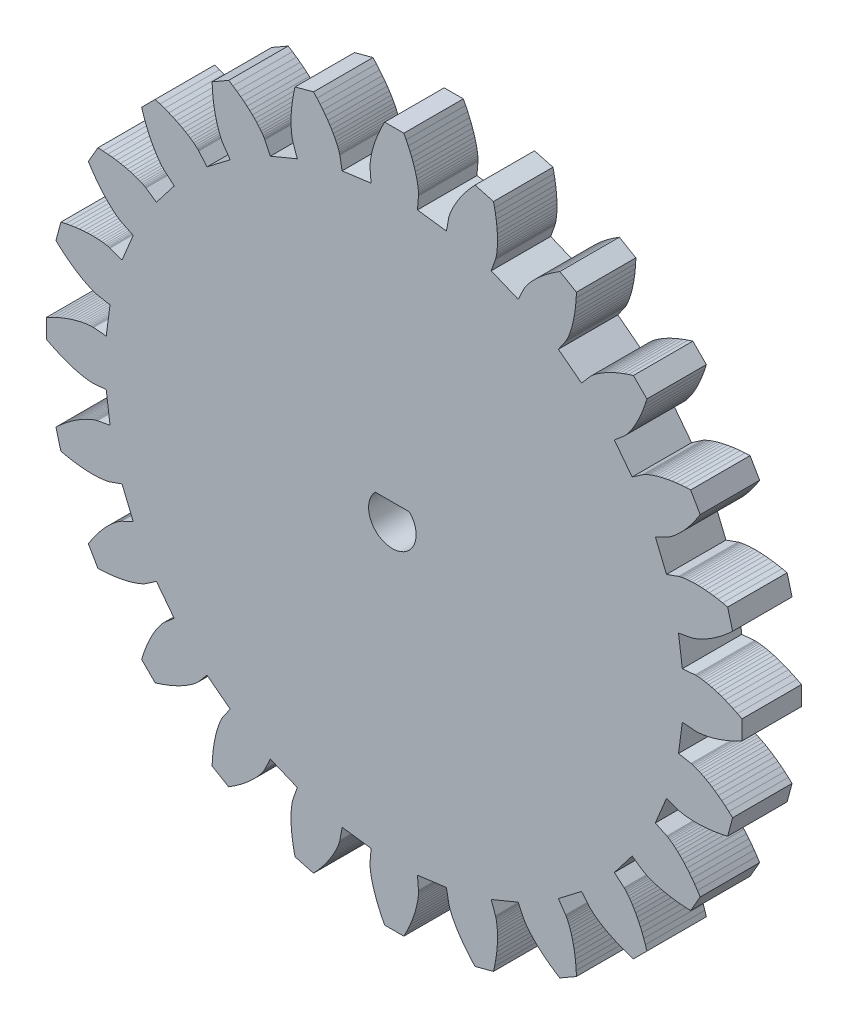
SolidWorks part; units mm, degrees
ref_plane "Front Plane" through (0, 0, 0) normal (0, 0, 1) x (1, 0, 0)
ref_plane "Top Plane" through (0, 0, 0) normal (0, 1, 0) x (1, 0, 0)
ref_plane "Right Plane" through (0, 0, 0) normal (1, 0, 0) x (0, 0, -1)
sketch "Model" plane through (0, 0, 0) normal (0, 0, 1) x (1, 0, 0)
  line L0 (24.2216, 1.9505) -> (25.2898, 2.0365)
  line L1 (25.2898, 2.0365) -> (25.3014, 2.0372)
  line L2 (25.3014, 2.0372) -> (25.3361, 2.0384)
  line L3 (25.3361, 2.0384) -> (25.3939, 2.0386)
  line L4 (25.3939, 2.0386) -> (25.4748, 2.0365)
  line L5 (25.4748, 2.0365) -> (25.5787, 2.0307)
  line L6 (25.5787, 2.0307) -> (25.7054, 2.0197)
  line L7 (25.7054, 2.0197) -> (25.8547, 2.0023)
  line L8 (25.8547, 2.0023) -> (26.0263, 1.977)
  line L9 (26.0263, 1.977) -> (26.2199, 1.9424)
  line L10 (26.2199, 1.9424) -> (26.4349, 1.8973)
  line L11 (26.4349, 1.8973) -> (26.671, 1.8403)
  line L12 (26.671, 1.8403) -> (26.9275, 1.7702)
  line L13 (26.9275, 1.7702) -> (27.2039, 1.6855)
  line L14 (27.2039, 1.6855) -> (27.4996, 1.5851)
  line L15 (27.4996, 1.5851) -> (27.8137, 1.4677)
  line L16 (27.8137, 1.4677) -> (28.1456, 1.3321)
  line L17 (28.1456, 1.3321) -> (28.4943, 1.1772)
  line L18 (28.4943, 1.1772) -> (28.8591, 1.0018)
  line L19 (28.8591, 1.0018) -> (29.2389, 0.8049)
  line L20 (29.2389, 0.8049) -> (29.2389, -0.8049)
  line L21 (29.2389, -0.8049) -> (28.8591, -1.0018)
  line L22 (28.8591, -1.0018) -> (28.4943, -1.1772)
  line L23 (28.4943, -1.1772) -> (28.1456, -1.3321)
  line L24 (28.1456, -1.3321) -> (27.8137, -1.4677)
  line L25 (27.8137, -1.4677) -> (27.4996, -1.5851)
  line L26 (27.4996, -1.5851) -> (27.2039, -1.6855)
  line L27 (27.2039, -1.6855) -> (26.9275, -1.7702)
  line L28 (26.9275, -1.7702) -> (26.671, -1.8403)
  line L29 (26.671, -1.8403) -> (26.4349, -1.8973)
  line L30 (26.4349, -1.8973) -> (26.2199, -1.9424)
  line L31 (26.2199, -1.9424) -> (26.0263, -1.977)
  line L32 (26.0263, -1.977) -> (25.8547, -2.0023)
  line L33 (25.8547, -2.0023) -> (25.7054, -2.0197)
  line L34 (25.7054, -2.0197) -> (25.5787, -2.0307)
  line L35 (25.5787, -2.0307) -> (25.4748, -2.0365)
  line L36 (25.4748, -2.0365) -> (25.3939, -2.0386)
  line L37 (25.3939, -2.0386) -> (25.3361, -2.0384)
  line L38 (25.3361, -2.0384) -> (25.3014, -2.0372)
  line L39 (25.3014, -2.0372) -> (25.2898, -2.0365)
  line L40 (25.2898, -2.0365) -> (24.2216, -1.9505)
  line L41 (24.2216, -1.9505) -> (23.9011, -4.385)
  line L42 (23.9011, -4.385) -> (24.9552, -4.5784)
  line L43 (24.9552, -4.5784) -> (24.9665, -4.5807)
  line L44 (24.9665, -4.5807) -> (25.0003, -4.5885)
  line L45 (25.0003, -4.5885) -> (25.0562, -4.6033)
  line L46 (25.0562, -4.6033) -> (25.1338, -4.6263)
  line L47 (25.1338, -4.6263) -> (25.2327, -4.6588)
  line L48 (25.2327, -4.6588) -> (25.3523, -4.7022)
  line L49 (25.3523, -4.7022) -> (25.492, -4.7576)
  line L50 (25.492, -4.7576) -> (25.6512, -4.8265)
  line L51 (25.6512, -4.8265) -> (25.8292, -4.91)
  line L52 (25.8292, -4.91) -> (26.0252, -5.0092)
  line L53 (26.0252, -5.0092) -> (26.2385, -5.1253)
  line L54 (26.2385, -5.1253) -> (26.4681, -5.2595)
  line L55 (26.4681, -5.2595) -> (26.7132, -5.4128)
  line L56 (26.7132, -5.4128) -> (26.9728, -5.5864)
  line L57 (26.9728, -5.5864) -> (27.2458, -5.781)
  line L58 (27.2458, -5.781) -> (27.5313, -5.9979)
  line L59 (27.5313, -5.9979) -> (27.8281, -6.2378)
  line L60 (27.8281, -6.2378) -> (28.135, -6.5016)
  line L61 (28.135, -6.5016) -> (28.4509, -6.7901)
  line L62 (28.4509, -6.7901) -> (28.0343, -8.3451)
  line L63 (28.0343, -8.3451) -> (27.6164, -8.437)
  line L64 (27.6164, -8.437) -> (27.2187, -8.512)
  line L65 (27.2187, -8.512) -> (26.8417, -8.5713)
  line L66 (26.8417, -8.5713) -> (26.4861, -8.6164)
  line L67 (26.4861, -8.6164) -> (26.1523, -8.6485)
  line L68 (26.1523, -8.6485) -> (25.8407, -8.6689)
  line L69 (25.8407, -8.6689) -> (25.5518, -8.6792)
  line L70 (25.5518, -8.6792) -> (25.2859, -8.6806)
  line L71 (25.2859, -8.6806) -> (25.0431, -8.6745)
  line L72 (25.0431, -8.6745) -> (24.8237, -8.6625)
  line L73 (24.8237, -8.6625) -> (24.6278, -8.6457)
  line L74 (24.6278, -8.6457) -> (24.4555, -8.6258)
  line L75 (24.4555, -8.6258) -> (24.3068, -8.604)
  line L76 (24.3068, -8.604) -> (24.1816, -8.5817)
  line L77 (24.1816, -8.5817) -> (24.0797, -8.5605)
  line L78 (24.0797, -8.5605) -> (24.001, -8.5416)
  line L79 (24.001, -8.5416) -> (23.9452, -8.5264)
  line L80 (23.9452, -8.5264) -> (23.912, -8.5163)
  line L81 (23.912, -8.5163) -> (23.901, -8.5126)
  line L82 (23.901, -8.5126) -> (22.8914, -8.1531)
  line L83 (22.8914, -8.1531) -> (21.9518, -10.4216)
  line L84 (21.9518, -10.4216) -> (22.9199, -10.8812)
  line L85 (22.9199, -10.8812) -> (22.9302, -10.8864)
  line L86 (22.9302, -10.8864) -> (22.9609, -10.9027)
  line L87 (22.9609, -10.9027) -> (23.011, -10.9314)
  line L88 (23.011, -10.9314) -> (23.0801, -10.9737)
  line L89 (23.0801, -10.9737) -> (23.1671, -11.0307)
  line L90 (23.1671, -11.0307) -> (23.2714, -11.1036)
  line L91 (23.2714, -11.1036) -> (23.392, -11.1933)
  line L92 (23.392, -11.1933) -> (23.528, -11.3011)
  line L93 (23.528, -11.3011) -> (23.6783, -11.4277)
  line L94 (23.6783, -11.4277) -> (23.842, -11.5743)
  line L95 (23.842, -11.5743) -> (24.0179, -11.7417)
  line L96 (24.0179, -11.7417) -> (24.205, -11.9308)
  line L97 (24.205, -11.9308) -> (24.402, -12.1423)
  line L98 (24.402, -12.1423) -> (24.6078, -12.3771)
  line L99 (24.6078, -12.3771) -> (24.8212, -12.6358)
  line L100 (24.8212, -12.6358) -> (25.0408, -12.9191)
  line L101 (25.0408, -12.9191) -> (25.2654, -13.2277)
  line L102 (25.2654, -13.2277) -> (25.4936, -13.5619)
  line L103 (25.4936, -13.5619) -> (25.7241, -13.9224)
  line L104 (25.7241, -13.9224) -> (24.9192, -15.3165)
  line L105 (24.9192, -15.3165) -> (24.4918, -15.2972)
  line L106 (24.4918, -15.2972) -> (24.0882, -15.2667)
  line L107 (24.0882, -15.2667) -> (23.7087, -15.2264)
  line L108 (23.7087, -15.2264) -> (23.3535, -15.1779)
  line L109 (23.3535, -15.1779) -> (23.0228, -15.1225)
  line L110 (23.0228, -15.1225) -> (22.7165, -15.0616)
  line L111 (22.7165, -15.0616) -> (22.4348, -14.9967)
  line L112 (22.4348, -14.9967) -> (22.1776, -14.9293)
  line L113 (22.1776, -14.9293) -> (21.9446, -14.8606)
  line L114 (21.9446, -14.8606) -> (21.7359, -14.7921)
  line L115 (21.7359, -14.7921) -> (21.551, -14.7253)
  line L116 (21.551, -14.7253) -> (21.3897, -14.6614)
  line L117 (21.3897, -14.6614) -> (21.2517, -14.6018)
  line L118 (21.2517, -14.6018) -> (21.1365, -14.548)
  line L119 (21.1365, -14.548) -> (21.0436, -14.5011)
  line L120 (21.0436, -14.5011) -> (20.9724, -14.4624)
  line L121 (20.9724, -14.4624) -> (20.9225, -14.4333)
  line L122 (20.9225, -14.4333) -> (20.893, -14.415)
  line L123 (20.893, -14.415) -> (20.8834, -14.4086)
  line L124 (20.8834, -14.4086) -> (20.0013, -13.8)
  line L125 (20.0013, -13.8) -> (18.5065, -15.748)
  line L126 (18.5065, -15.748) -> (19.3227, -16.4426)
  line L127 (19.3227, -16.4426) -> (19.3313, -16.4502)
  line L128 (19.3313, -16.4502) -> (19.3566, -16.4739)
  line L129 (19.3566, -16.4739) -> (19.3977, -16.5147)
  line L130 (19.3977, -16.5147) -> (19.4534, -16.5734)
  line L131 (19.4534, -16.5734) -> (19.5228, -16.651)
  line L132 (19.5228, -16.651) -> (19.6046, -16.7483)
  line L133 (19.6046, -16.7483) -> (19.6979, -16.8662)
  line L134 (19.6979, -16.8662) -> (19.8013, -17.0055)
  line L135 (19.8013, -17.0055) -> (19.9138, -17.1667)
  line L136 (19.9138, -17.1667) -> (20.0339, -17.3507)
  line L137 (20.0339, -17.3507) -> (20.1605, -17.5579)
  line L138 (20.1605, -17.5579) -> (20.2923, -17.7889)
  line L139 (20.2923, -17.7889) -> (20.4279, -18.0443)
  line L140 (20.4279, -18.0443) -> (20.5659, -18.3243)
  line L141 (20.5659, -18.3243) -> (20.7051, -18.6294)
  line L142 (20.7051, -18.6294) -> (20.8439, -18.96)
  line L143 (20.8439, -18.96) -> (20.9809, -19.3161)
  line L144 (20.9809, -19.3161) -> (21.1149, -19.698)
  line L145 (21.1149, -19.698) -> (21.2442, -20.1059)
  line L146 (21.2442, -20.1059) -> (20.1059, -21.2442)
  line L147 (20.1059, -21.2442) -> (19.698, -21.1149)
  line L148 (19.698, -21.1149) -> (19.3161, -20.9809)
  line L149 (19.3161, -20.9809) -> (18.96, -20.8439)
  line L150 (18.96, -20.8439) -> (18.6294, -20.7051)
  line L151 (18.6294, -20.7051) -> (18.3243, -20.5659)
  line L152 (18.3243, -20.5659) -> (18.0443, -20.4279)
  line L153 (18.0443, -20.4279) -> (17.7889, -20.2923)
  line L154 (17.7889, -20.2923) -> (17.5579, -20.1605)
  line L155 (17.5579, -20.1605) -> (17.3507, -20.0339)
  line L156 (17.3507, -20.0339) -> (17.1667, -19.9138)
  line L157 (17.1667, -19.9138) -> (17.0055, -19.8013)
  line L158 (17.0055, -19.8013) -> (16.8662, -19.6979)
  line L159 (16.8662, -19.6979) -> (16.7483, -19.6046)
  line L160 (16.7483, -19.6046) -> (16.651, -19.5228)
  line L161 (16.651, -19.5228) -> (16.5734, -19.4534)
  line L162 (16.5734, -19.4534) -> (16.5147, -19.3977)
  line L163 (16.5147, -19.3977) -> (16.4739, -19.3566)
  line L164 (16.4739, -19.3566) -> (16.4502, -19.3313)
  line L165 (16.4502, -19.3313) -> (16.4426, -19.3227)
  line L166 (16.4426, -19.3227) -> (15.748, -18.5065)
  line L167 (15.748, -18.5065) -> (13.8, -20.0013)
  line L168 (13.8, -20.0013) -> (14.4086, -20.8834)
  line L169 (14.4086, -20.8834) -> (14.415, -20.893)
  line L170 (14.415, -20.893) -> (14.4333, -20.9225)
  line L171 (14.4333, -20.9225) -> (14.4624, -20.9724)
  line L172 (14.4624, -20.9724) -> (14.5011, -21.0436)
  line L173 (14.5011, -21.0436) -> (14.548, -21.1365)
  line L174 (14.548, -21.1365) -> (14.6018, -21.2517)
  line L175 (14.6018, -21.2517) -> (14.6614, -21.3897)
  line L176 (14.6614, -21.3897) -> (14.7253, -21.551)
  line L177 (14.7253, -21.551) -> (14.7921, -21.7359)
  line L178 (14.7921, -21.7359) -> (14.8606, -21.9446)
  line L179 (14.8606, -21.9446) -> (14.9293, -22.1776)
  line L180 (14.9293, -22.1776) -> (14.9967, -22.4348)
  line L181 (14.9967, -22.4348) -> (15.0616, -22.7165)
  line L182 (15.0616, -22.7165) -> (15.1225, -23.0228)
  line L183 (15.1225, -23.0228) -> (15.1779, -23.3535)
  line L184 (15.1779, -23.3535) -> (15.2264, -23.7087)
  line L185 (15.2264, -23.7087) -> (15.2667, -24.0882)
  line L186 (15.2667, -24.0882) -> (15.2972, -24.4918)
  line L187 (15.2972, -24.4918) -> (15.3165, -24.9192)
  line L188 (15.3165, -24.9192) -> (13.9224, -25.7241)
  line L189 (13.9224, -25.7241) -> (13.5619, -25.4936)
  line L190 (13.5619, -25.4936) -> (13.2277, -25.2654)
  line L191 (13.2277, -25.2654) -> (12.9191, -25.0408)
  line L192 (12.9191, -25.0408) -> (12.6358, -24.8212)
  line L193 (12.6358, -24.8212) -> (12.3771, -24.6078)
  line L194 (12.3771, -24.6078) -> (12.1423, -24.402)
  line L195 (12.1423, -24.402) -> (11.9308, -24.205)
  line L196 (11.9308, -24.205) -> (11.7417, -24.0179)
  line L197 (11.7417, -24.0179) -> (11.5743, -23.842)
  line L198 (11.5743, -23.842) -> (11.4277, -23.6783)
  line L199 (11.4277, -23.6783) -> (11.3011, -23.528)
  line L200 (11.3011, -23.528) -> (11.1933, -23.392)
  line L201 (11.1933, -23.392) -> (11.1036, -23.2714)
  line L202 (11.1036, -23.2714) -> (11.0307, -23.1671)
  line L203 (11.0307, -23.1671) -> (10.9737, -23.0801)
  line L204 (10.9737, -23.0801) -> (10.9314, -23.011)
  line L205 (10.9314, -23.011) -> (10.9027, -22.9609)
  line L206 (10.9027, -22.9609) -> (10.8864, -22.9302)
  line L207 (10.8864, -22.9302) -> (10.8812, -22.9199)
  line L208 (10.8812, -22.9199) -> (10.4216, -21.9518)
  line L209 (10.4216, -21.9518) -> (8.1531, -22.8914)
  line L210 (8.1531, -22.8914) -> (8.5126, -23.901)
  line L211 (8.5126, -23.901) -> (8.5163, -23.912)
  line L212 (8.5163, -23.912) -> (8.5264, -23.9452)
  line L213 (8.5264, -23.9452) -> (8.5416, -24.001)
  line L214 (8.5416, -24.001) -> (8.5605, -24.0797)
  line L215 (8.5605, -24.0797) -> (8.5817, -24.1816)
  line L216 (8.5817, -24.1816) -> (8.604, -24.3068)
  line L217 (8.604, -24.3068) -> (8.6258, -24.4555)
  line L218 (8.6258, -24.4555) -> (8.6457, -24.6278)
  line L219 (8.6457, -24.6278) -> (8.6625, -24.8237)
  line L220 (8.6625, -24.8237) -> (8.6745, -25.0431)
  line L221 (8.6745, -25.0431) -> (8.6806, -25.2859)
  line L222 (8.6806, -25.2859) -> (8.6792, -25.5518)
  line L223 (8.6792, -25.5518) -> (8.6689, -25.8407)
  line L224 (8.6689, -25.8407) -> (8.6485, -26.1523)
  line L225 (8.6485, -26.1523) -> (8.6164, -26.4861)
  line L226 (8.6164, -26.4861) -> (8.5713, -26.8417)
  line L227 (8.5713, -26.8417) -> (8.512, -27.2187)
  line L228 (8.512, -27.2187) -> (8.437, -27.6164)
  line L229 (8.437, -27.6164) -> (8.3451, -28.0343)
  line L230 (8.3451, -28.0343) -> (6.7901, -28.4509)
  line L231 (6.7901, -28.4509) -> (6.5016, -28.135)
  line L232 (6.5016, -28.135) -> (6.2378, -27.8281)
  line L233 (6.2378, -27.8281) -> (5.9979, -27.5313)
  line L234 (5.9979, -27.5313) -> (5.781, -27.2458)
  line L235 (5.781, -27.2458) -> (5.5864, -26.9728)
  line L236 (5.5864, -26.9728) -> (5.4128, -26.7132)
  line L237 (5.4128, -26.7132) -> (5.2595, -26.4681)
  line L238 (5.2595, -26.4681) -> (5.1253, -26.2385)
  line L239 (5.1253, -26.2385) -> (5.0092, -26.0252)
  line L240 (5.0092, -26.0252) -> (4.91, -25.8292)
  line L241 (4.91, -25.8292) -> (4.8265, -25.6512)
  line L242 (4.8265, -25.6512) -> (4.7576, -25.492)
  line L243 (4.7576, -25.492) -> (4.7022, -25.3523)
  line L244 (4.7022, -25.3523) -> (4.6588, -25.2327)
  line L245 (4.6588, -25.2327) -> (4.6263, -25.1338)
  line L246 (4.6263, -25.1338) -> (4.6033, -25.0562)
  line L247 (4.6033, -25.0562) -> (4.5885, -25.0003)
  line L248 (4.5885, -25.0003) -> (4.5807, -24.9665)
  line L249 (4.5807, -24.9665) -> (4.5784, -24.9552)
  line L250 (4.5784, -24.9552) -> (4.385, -23.9011)
  line L251 (4.385, -23.9011) -> (1.9505, -24.2216)
  line L252 (1.9505, -24.2216) -> (2.0365, -25.2898)
  line L253 (2.0365, -25.2898) -> (2.0372, -25.3014)
  line L254 (2.0372, -25.3014) -> (2.0384, -25.3361)
  line L255 (2.0384, -25.3361) -> (2.0386, -25.3939)
  line L256 (2.0386, -25.3939) -> (2.0365, -25.4748)
  line L257 (2.0365, -25.4748) -> (2.0307, -25.5787)
  line L258 (2.0307, -25.5787) -> (2.0197, -25.7054)
  line L259 (2.0197, -25.7054) -> (2.0023, -25.8547)
  line L260 (2.0023, -25.8547) -> (1.977, -26.0263)
  line L261 (1.977, -26.0263) -> (1.9424, -26.2199)
  line L262 (1.9424, -26.2199) -> (1.8973, -26.4349)
  line L263 (1.8973, -26.4349) -> (1.8403, -26.671)
  line L264 (1.8403, -26.671) -> (1.7702, -26.9275)
  line L265 (1.7702, -26.9275) -> (1.6855, -27.2039)
  line L266 (1.6855, -27.2039) -> (1.5851, -27.4996)
  line L267 (1.5851, -27.4996) -> (1.4677, -27.8137)
  line L268 (1.4677, -27.8137) -> (1.3321, -28.1456)
  line L269 (1.3321, -28.1456) -> (1.1772, -28.4943)
  line L270 (1.1772, -28.4943) -> (1.0018, -28.8591)
  line L271 (1.0018, -28.8591) -> (0.8049, -29.2389)
  line L272 (0.8049, -29.2389) -> (-0.8049, -29.2389)
  line L273 (-0.8049, -29.2389) -> (-1.0018, -28.8591)
  line L274 (-1.0018, -28.8591) -> (-1.1772, -28.4943)
  line L275 (-1.1772, -28.4943) -> (-1.3321, -28.1456)
  line L276 (-1.3321, -28.1456) -> (-1.4677, -27.8137)
  line L277 (-1.4677, -27.8137) -> (-1.5851, -27.4996)
  line L278 (-1.5851, -27.4996) -> (-1.6855, -27.2039)
  line L279 (-1.6855, -27.2039) -> (-1.7702, -26.9275)
  line L280 (-1.7702, -26.9275) -> (-1.8403, -26.671)
  line L281 (-1.8403, -26.671) -> (-1.8973, -26.4349)
  line L282 (-1.8973, -26.4349) -> (-1.9424, -26.2199)
  line L283 (-1.9424, -26.2199) -> (-1.977, -26.0263)
  line L284 (-1.977, -26.0263) -> (-2.0023, -25.8547)
  line L285 (-2.0023, -25.8547) -> (-2.0197, -25.7054)
  line L286 (-2.0197, -25.7054) -> (-2.0307, -25.5787)
  line L287 (-2.0307, -25.5787) -> (-2.0365, -25.4748)
  line L288 (-2.0365, -25.4748) -> (-2.0386, -25.3939)
  line L289 (-2.0386, -25.3939) -> (-2.0384, -25.3361)
  line L290 (-2.0384, -25.3361) -> (-2.0372, -25.3014)
  line L291 (-2.0372, -25.3014) -> (-2.0365, -25.2898)
  line L292 (-2.0365, -25.2898) -> (-1.9505, -24.2216)
  line L293 (-1.9505, -24.2216) -> (-4.385, -23.9011)
  line L294 (-4.385, -23.9011) -> (-4.5784, -24.9552)
  line L295 (-4.5784, -24.9552) -> (-4.5807, -24.9665)
  line L296 (-4.5807, -24.9665) -> (-4.5885, -25.0003)
  line L297 (-4.5885, -25.0003) -> (-4.6033, -25.0562)
  line L298 (-4.6033, -25.0562) -> (-4.6263, -25.1338)
  line L299 (-4.6263, -25.1338) -> (-4.6588, -25.2327)
  line L300 (-4.6588, -25.2327) -> (-4.7022, -25.3523)
  line L301 (-4.7022, -25.3523) -> (-4.7576, -25.492)
  line L302 (-4.7576, -25.492) -> (-4.8265, -25.6512)
  line L303 (-4.8265, -25.6512) -> (-4.91, -25.8292)
  line L304 (-4.91, -25.8292) -> (-5.0092, -26.0252)
  line L305 (-5.0092, -26.0252) -> (-5.1253, -26.2385)
  line L306 (-5.1253, -26.2385) -> (-5.2595, -26.4681)
  line L307 (-5.2595, -26.4681) -> (-5.4128, -26.7132)
  line L308 (-5.4128, -26.7132) -> (-5.5864, -26.9728)
  line L309 (-5.5864, -26.9728) -> (-5.781, -27.2458)
  line L310 (-5.781, -27.2458) -> (-5.9979, -27.5313)
  line L311 (-5.9979, -27.5313) -> (-6.2378, -27.8281)
  line L312 (-6.2378, -27.8281) -> (-6.5016, -28.135)
  line L313 (-6.5016, -28.135) -> (-6.7901, -28.4509)
  line L314 (-6.7901, -28.4509) -> (-8.3451, -28.0343)
  line L315 (-8.3451, -28.0343) -> (-8.437, -27.6164)
  line L316 (-8.437, -27.6164) -> (-8.512, -27.2187)
  line L317 (-8.512, -27.2187) -> (-8.5713, -26.8417)
  line L318 (-8.5713, -26.8417) -> (-8.6164, -26.4861)
  line L319 (-8.6164, -26.4861) -> (-8.6485, -26.1523)
  line L320 (-8.6485, -26.1523) -> (-8.6689, -25.8407)
  line L321 (-8.6689, -25.8407) -> (-8.6792, -25.5518)
  line L322 (-8.6792, -25.5518) -> (-8.6806, -25.2859)
  line L323 (-8.6806, -25.2859) -> (-8.6745, -25.0431)
  line L324 (-8.6745, -25.0431) -> (-8.6625, -24.8237)
  line L325 (-8.6625, -24.8237) -> (-8.6457, -24.6278)
  line L326 (-8.6457, -24.6278) -> (-8.6258, -24.4555)
  line L327 (-8.6258, -24.4555) -> (-8.604, -24.3068)
  line L328 (-8.604, -24.3068) -> (-8.5817, -24.1816)
  line L329 (-8.5817, -24.1816) -> (-8.5605, -24.0797)
  line L330 (-8.5605, -24.0797) -> (-8.5416, -24.001)
  line L331 (-8.5416, -24.001) -> (-8.5264, -23.9452)
  line L332 (-8.5264, -23.9452) -> (-8.5163, -23.912)
  line L333 (-8.5163, -23.912) -> (-8.5126, -23.901)
  line L334 (-8.5126, -23.901) -> (-8.1531, -22.8914)
  line L335 (-8.1531, -22.8914) -> (-10.4216, -21.9518)
  line L336 (-10.4216, -21.9518) -> (-10.8812, -22.9199)
  line L337 (-10.8812, -22.9199) -> (-10.8864, -22.9302)
  line L338 (-10.8864, -22.9302) -> (-10.9027, -22.9609)
  line L339 (-10.9027, -22.9609) -> (-10.9314, -23.011)
  line L340 (-10.9314, -23.011) -> (-10.9737, -23.0801)
  line L341 (-10.9737, -23.0801) -> (-11.0307, -23.1671)
  line L342 (-11.0307, -23.1671) -> (-11.1036, -23.2714)
  line L343 (-11.1036, -23.2714) -> (-11.1933, -23.392)
  line L344 (-11.1933, -23.392) -> (-11.3011, -23.528)
  line L345 (-11.3011, -23.528) -> (-11.4277, -23.6783)
  line L346 (-11.4277, -23.6783) -> (-11.5743, -23.842)
  line L347 (-11.5743, -23.842) -> (-11.7417, -24.0179)
  line L348 (-11.7417, -24.0179) -> (-11.9308, -24.205)
  line L349 (-11.9308, -24.205) -> (-12.1423, -24.402)
  line L350 (-12.1423, -24.402) -> (-12.3771, -24.6078)
  line L351 (-12.3771, -24.6078) -> (-12.6358, -24.8212)
  line L352 (-12.6358, -24.8212) -> (-12.9191, -25.0408)
  line L353 (-12.9191, -25.0408) -> (-13.2277, -25.2654)
  line L354 (-13.2277, -25.2654) -> (-13.5619, -25.4936)
  line L355 (-13.5619, -25.4936) -> (-13.9224, -25.7241)
  line L356 (-13.9224, -25.7241) -> (-15.3165, -24.9192)
  line L357 (-15.3165, -24.9192) -> (-15.2972, -24.4918)
  line L358 (-15.2972, -24.4918) -> (-15.2667, -24.0882)
  line L359 (-15.2667, -24.0882) -> (-15.2264, -23.7087)
  line L360 (-15.2264, -23.7087) -> (-15.1779, -23.3535)
  line L361 (-15.1779, -23.3535) -> (-15.1225, -23.0228)
  line L362 (-15.1225, -23.0228) -> (-15.0616, -22.7165)
  line L363 (-15.0616, -22.7165) -> (-14.9967, -22.4348)
  line L364 (-14.9967, -22.4348) -> (-14.9293, -22.1776)
  line L365 (-14.9293, -22.1776) -> (-14.8606, -21.9446)
  line L366 (-14.8606, -21.9446) -> (-14.7921, -21.7359)
  line L367 (-14.7921, -21.7359) -> (-14.7253, -21.551)
  line L368 (-14.7253, -21.551) -> (-14.6614, -21.3897)
  line L369 (-14.6614, -21.3897) -> (-14.6018, -21.2517)
  line L370 (-14.6018, -21.2517) -> (-14.548, -21.1365)
  line L371 (-14.548, -21.1365) -> (-14.5011, -21.0436)
  line L372 (-14.5011, -21.0436) -> (-14.4624, -20.9724)
  line L373 (-14.4624, -20.9724) -> (-14.4333, -20.9225)
  line L374 (-14.4333, -20.9225) -> (-14.415, -20.893)
  line L375 (-14.415, -20.893) -> (-14.4086, -20.8834)
  line L376 (-14.4086, -20.8834) -> (-13.8, -20.0013)
  line L377 (-13.8, -20.0013) -> (-15.748, -18.5065)
  line L378 (-15.748, -18.5065) -> (-16.4426, -19.3227)
  line L379 (-16.4426, -19.3227) -> (-16.4502, -19.3313)
  line L380 (-16.4502, -19.3313) -> (-16.4739, -19.3566)
  line L381 (-16.4739, -19.3566) -> (-16.5147, -19.3977)
  line L382 (-16.5147, -19.3977) -> (-16.5734, -19.4534)
  line L383 (-16.5734, -19.4534) -> (-16.651, -19.5228)
  line L384 (-16.651, -19.5228) -> (-16.7483, -19.6046)
  line L385 (-16.7483, -19.6046) -> (-16.8662, -19.6979)
  line L386 (-16.8662, -19.6979) -> (-17.0055, -19.8013)
  line L387 (-17.0055, -19.8013) -> (-17.1667, -19.9138)
  line L388 (-17.1667, -19.9138) -> (-17.3507, -20.0339)
  line L389 (-17.3507, -20.0339) -> (-17.5579, -20.1605)
  line L390 (-17.5579, -20.1605) -> (-17.7889, -20.2923)
  line L391 (-17.7889, -20.2923) -> (-18.0443, -20.4279)
  line L392 (-18.0443, -20.4279) -> (-18.3243, -20.5659)
  line L393 (-18.3243, -20.5659) -> (-18.6294, -20.7051)
  line L394 (-18.6294, -20.7051) -> (-18.96, -20.8439)
  line L395 (-18.96, -20.8439) -> (-19.3161, -20.9809)
  line L396 (-19.3161, -20.9809) -> (-19.698, -21.1149)
  line L397 (-19.698, -21.1149) -> (-20.1059, -21.2442)
  line L398 (-20.1059, -21.2442) -> (-21.2442, -20.1059)
  line L399 (-21.2442, -20.1059) -> (-21.1149, -19.698)
  line L400 (-21.1149, -19.698) -> (-20.9809, -19.3161)
  line L401 (-20.9809, -19.3161) -> (-20.8439, -18.96)
  line L402 (-20.8439, -18.96) -> (-20.7051, -18.6294)
  line L403 (-20.7051, -18.6294) -> (-20.5659, -18.3243)
  line L404 (-20.5659, -18.3243) -> (-20.4279, -18.0443)
  line L405 (-20.4279, -18.0443) -> (-20.2923, -17.7889)
  line L406 (-20.2923, -17.7889) -> (-20.1605, -17.5579)
  line L407 (-20.1605, -17.5579) -> (-20.0339, -17.3507)
  line L408 (-20.0339, -17.3507) -> (-19.9138, -17.1667)
  line L409 (-19.9138, -17.1667) -> (-19.8013, -17.0055)
  line L410 (-19.8013, -17.0055) -> (-19.6979, -16.8662)
  line L411 (-19.6979, -16.8662) -> (-19.6046, -16.7483)
  line L412 (-19.6046, -16.7483) -> (-19.5228, -16.651)
  line L413 (-19.5228, -16.651) -> (-19.4534, -16.5734)
  line L414 (-19.4534, -16.5734) -> (-19.3977, -16.5147)
  line L415 (-19.3977, -16.5147) -> (-19.3566, -16.4739)
  line L416 (-19.3566, -16.4739) -> (-19.3313, -16.4502)
  line L417 (-19.3313, -16.4502) -> (-19.3227, -16.4426)
  line L418 (-19.3227, -16.4426) -> (-18.5065, -15.748)
  line L419 (-18.5065, -15.748) -> (-20.0013, -13.8)
  line L420 (-20.0013, -13.8) -> (-20.8834, -14.4086)
  line L421 (-20.8834, -14.4086) -> (-20.893, -14.415)
  line L422 (-20.893, -14.415) -> (-20.9225, -14.4333)
  line L423 (-20.9225, -14.4333) -> (-20.9724, -14.4624)
  line L424 (-20.9724, -14.4624) -> (-21.0436, -14.5011)
  line L425 (-21.0436, -14.5011) -> (-21.1365, -14.548)
  line L426 (-21.1365, -14.548) -> (-21.2517, -14.6018)
  line L427 (-21.2517, -14.6018) -> (-21.3897, -14.6614)
  line L428 (-21.3897, -14.6614) -> (-21.551, -14.7253)
  line L429 (-21.551, -14.7253) -> (-21.7359, -14.7921)
  line L430 (-21.7359, -14.7921) -> (-21.9446, -14.8606)
  line L431 (-21.9446, -14.8606) -> (-22.1776, -14.9293)
  line L432 (-22.1776, -14.9293) -> (-22.4348, -14.9967)
  line L433 (-22.4348, -14.9967) -> (-22.7165, -15.0616)
  line L434 (-22.7165, -15.0616) -> (-23.0228, -15.1225)
  line L435 (-23.0228, -15.1225) -> (-23.3535, -15.1779)
  line L436 (-23.3535, -15.1779) -> (-23.7087, -15.2264)
  line L437 (-23.7087, -15.2264) -> (-24.0882, -15.2667)
  line L438 (-24.0882, -15.2667) -> (-24.4918, -15.2972)
  line L439 (-24.4918, -15.2972) -> (-24.9192, -15.3165)
  line L440 (-24.9192, -15.3165) -> (-25.7241, -13.9224)
  line L441 (-25.7241, -13.9224) -> (-25.4936, -13.5619)
  line L442 (-25.4936, -13.5619) -> (-25.2654, -13.2277)
  line L443 (-25.2654, -13.2277) -> (-25.0408, -12.9191)
  line L444 (-25.0408, -12.9191) -> (-24.8212, -12.6358)
  line L445 (-24.8212, -12.6358) -> (-24.6078, -12.3771)
  line L446 (-24.6078, -12.3771) -> (-24.402, -12.1423)
  line L447 (-24.402, -12.1423) -> (-24.205, -11.9308)
  line L448 (-24.205, -11.9308) -> (-24.0179, -11.7417)
  line L449 (-24.0179, -11.7417) -> (-23.842, -11.5743)
  line L450 (-23.842, -11.5743) -> (-23.6783, -11.4277)
  line L451 (-23.6783, -11.4277) -> (-23.528, -11.3011)
  line L452 (-23.528, -11.3011) -> (-23.392, -11.1933)
  line L453 (-23.392, -11.1933) -> (-23.2714, -11.1036)
  line L454 (-23.2714, -11.1036) -> (-23.1671, -11.0307)
  line L455 (-23.1671, -11.0307) -> (-23.0801, -10.9737)
  line L456 (-23.0801, -10.9737) -> (-23.011, -10.9314)
  line L457 (-23.011, -10.9314) -> (-22.9609, -10.9027)
  line L458 (-22.9609, -10.9027) -> (-22.9302, -10.8864)
  line L459 (-22.9302, -10.8864) -> (-22.9199, -10.8812)
  line L460 (-22.9199, -10.8812) -> (-21.9518, -10.4216)
  line L461 (-21.9518, -10.4216) -> (-22.8914, -8.1531)
  line L462 (-22.8914, -8.1531) -> (-23.901, -8.5126)
  line L463 (-23.901, -8.5126) -> (-23.912, -8.5163)
  line L464 (-23.912, -8.5163) -> (-23.9452, -8.5264)
  line L465 (-23.9452, -8.5264) -> (-24.001, -8.5416)
  line L466 (-24.001, -8.5416) -> (-24.0797, -8.5605)
  line L467 (-24.0797, -8.5605) -> (-24.1816, -8.5817)
  line L468 (-24.1816, -8.5817) -> (-24.3068, -8.604)
  line L469 (-24.3068, -8.604) -> (-24.4555, -8.6258)
  line L470 (-24.4555, -8.6258) -> (-24.6278, -8.6457)
  line L471 (-24.6278, -8.6457) -> (-24.8237, -8.6625)
  line L472 (-24.8237, -8.6625) -> (-25.0431, -8.6745)
  line L473 (-25.0431, -8.6745) -> (-25.2859, -8.6806)
  line L474 (-25.2859, -8.6806) -> (-25.5518, -8.6792)
  line L475 (-25.5518, -8.6792) -> (-25.8407, -8.6689)
  line L476 (-25.8407, -8.6689) -> (-26.1523, -8.6485)
  line L477 (-26.1523, -8.6485) -> (-26.4861, -8.6164)
  line L478 (-26.4861, -8.6164) -> (-26.8417, -8.5713)
  line L479 (-26.8417, -8.5713) -> (-27.2187, -8.512)
  line L480 (-27.2187, -8.512) -> (-27.6164, -8.437)
  line L481 (-27.6164, -8.437) -> (-28.0343, -8.3451)
  line L482 (-28.0343, -8.3451) -> (-28.4509, -6.7901)
  line L483 (-28.4509, -6.7901) -> (-28.135, -6.5016)
  line L484 (-28.135, -6.5016) -> (-27.8281, -6.2378)
  line L485 (-27.8281, -6.2378) -> (-27.5313, -5.9979)
  line L486 (-27.5313, -5.9979) -> (-27.2458, -5.781)
  line L487 (-27.2458, -5.781) -> (-26.9728, -5.5864)
  line L488 (-26.9728, -5.5864) -> (-26.7132, -5.4128)
  line L489 (-26.7132, -5.4128) -> (-26.4681, -5.2595)
  line L490 (-26.4681, -5.2595) -> (-26.2385, -5.1253)
  line L491 (-26.2385, -5.1253) -> (-26.0252, -5.0092)
  line L492 (-26.0252, -5.0092) -> (-25.8292, -4.91)
  line L493 (-25.8292, -4.91) -> (-25.6512, -4.8265)
  line L494 (-25.6512, -4.8265) -> (-25.492, -4.7576)
  line L495 (-25.492, -4.7576) -> (-25.3523, -4.7022)
  line L496 (-25.3523, -4.7022) -> (-25.2327, -4.6588)
  line L497 (-25.2327, -4.6588) -> (-25.1338, -4.6263)
  line L498 (-25.1338, -4.6263) -> (-25.0562, -4.6033)
  line L499 (-25.0562, -4.6033) -> (-25.0003, -4.5885)
  line L500 (-25.0003, -4.5885) -> (-24.9665, -4.5807)
  line L501 (-24.9665, -4.5807) -> (-24.9552, -4.5784)
  line L502 (-24.9552, -4.5784) -> (-23.9011, -4.385)
  line L503 (-23.9011, -4.385) -> (-24.2216, -1.9505)
  line L504 (-24.2216, -1.9505) -> (-25.2898, -2.0365)
  line L505 (-25.2898, -2.0365) -> (-25.3014, -2.0372)
  line L506 (-25.3014, -2.0372) -> (-25.3361, -2.0384)
  line L507 (-25.3361, -2.0384) -> (-25.3939, -2.0386)
  line L508 (-25.3939, -2.0386) -> (-25.4748, -2.0365)
  line L509 (-25.4748, -2.0365) -> (-25.5787, -2.0307)
  line L510 (-25.5787, -2.0307) -> (-25.7054, -2.0197)
  line L511 (-25.7054, -2.0197) -> (-25.8547, -2.0023)
  line L512 (-25.8547, -2.0023) -> (-26.0263, -1.977)
  line L513 (-26.0263, -1.977) -> (-26.2199, -1.9424)
  line L514 (-26.2199, -1.9424) -> (-26.4349, -1.8973)
  line L515 (-26.4349, -1.8973) -> (-26.671, -1.8403)
  line L516 (-26.671, -1.8403) -> (-26.9275, -1.7702)
  line L517 (-26.9275, -1.7702) -> (-27.2039, -1.6855)
  line L518 (-27.2039, -1.6855) -> (-27.4996, -1.5851)
  line L519 (-27.4996, -1.5851) -> (-27.8137, -1.4677)
  line L520 (-27.8137, -1.4677) -> (-28.1456, -1.3321)
  line L521 (-28.1456, -1.3321) -> (-28.4943, -1.1772)
  line L522 (-28.4943, -1.1772) -> (-28.8591, -1.0018)
  line L523 (-28.8591, -1.0018) -> (-29.2389, -0.8049)
  line L524 (-29.2389, -0.8049) -> (-29.2389, 0.8049)
  line L525 (-29.2389, 0.8049) -> (-28.8591, 1.0018)
  line L526 (-28.8591, 1.0018) -> (-28.4943, 1.1772)
  line L527 (-28.4943, 1.1772) -> (-28.1456, 1.3321)
  line L528 (-28.1456, 1.3321) -> (-27.8137, 1.4677)
  line L529 (-27.8137, 1.4677) -> (-27.4996, 1.5851)
  line L530 (-27.4996, 1.5851) -> (-27.2039, 1.6855)
  line L531 (-27.2039, 1.6855) -> (-26.9275, 1.7702)
  line L532 (-26.9275, 1.7702) -> (-26.671, 1.8403)
  line L533 (-26.671, 1.8403) -> (-26.4349, 1.8973)
  line L534 (-26.4349, 1.8973) -> (-26.2199, 1.9424)
  line L535 (-26.2199, 1.9424) -> (-26.0263, 1.977)
  line L536 (-26.0263, 1.977) -> (-25.8547, 2.0023)
  line L537 (-25.8547, 2.0023) -> (-25.7054, 2.0197)
  line L538 (-25.7054, 2.0197) -> (-25.5787, 2.0307)
  line L539 (-25.5787, 2.0307) -> (-25.4748, 2.0365)
  line L540 (-25.4748, 2.0365) -> (-25.3939, 2.0386)
  line L541 (-25.3939, 2.0386) -> (-25.3361, 2.0384)
  line L542 (-25.3361, 2.0384) -> (-25.3014, 2.0372)
  line L543 (-25.3014, 2.0372) -> (-25.2898, 2.0365)
  line L544 (-25.2898, 2.0365) -> (-24.2216, 1.9505)
  line L545 (-24.2216, 1.9505) -> (-23.9011, 4.385)
  line L546 (-23.9011, 4.385) -> (-24.9552, 4.5784)
  line L547 (-24.9552, 4.5784) -> (-24.9665, 4.5807)
  line L548 (-24.9665, 4.5807) -> (-25.0003, 4.5885)
  line L549 (-25.0003, 4.5885) -> (-25.0562, 4.6033)
  line L550 (-25.0562, 4.6033) -> (-25.1338, 4.6263)
  line L551 (-25.1338, 4.6263) -> (-25.2327, 4.6588)
  line L552 (-25.2327, 4.6588) -> (-25.3523, 4.7022)
  line L553 (-25.3523, 4.7022) -> (-25.492, 4.7576)
  line L554 (-25.492, 4.7576) -> (-25.6512, 4.8265)
  line L555 (-25.6512, 4.8265) -> (-25.8292, 4.91)
  line L556 (-25.8292, 4.91) -> (-26.0252, 5.0092)
  line L557 (-26.0252, 5.0092) -> (-26.2385, 5.1253)
  line L558 (-26.2385, 5.1253) -> (-26.4681, 5.2595)
  line L559 (-26.4681, 5.2595) -> (-26.7132, 5.4128)
  line L560 (-26.7132, 5.4128) -> (-26.9728, 5.5864)
  line L561 (-26.9728, 5.5864) -> (-27.2458, 5.781)
  line L562 (-27.2458, 5.781) -> (-27.5313, 5.9979)
  line L563 (-27.5313, 5.9979) -> (-27.8281, 6.2378)
  line L564 (-27.8281, 6.2378) -> (-28.135, 6.5016)
  line L565 (-28.135, 6.5016) -> (-28.4509, 6.7901)
  line L566 (-28.4509, 6.7901) -> (-28.0343, 8.3451)
  line L567 (-28.0343, 8.3451) -> (-27.6164, 8.437)
  line L568 (-27.6164, 8.437) -> (-27.2187, 8.512)
  line L569 (-27.2187, 8.512) -> (-26.8417, 8.5713)
  line L570 (-26.8417, 8.5713) -> (-26.4861, 8.6164)
  line L571 (-26.4861, 8.6164) -> (-26.1523, 8.6485)
  line L572 (-26.1523, 8.6485) -> (-25.8407, 8.6689)
  line L573 (-25.8407, 8.6689) -> (-25.5518, 8.6792)
  line L574 (-25.5518, 8.6792) -> (-25.2859, 8.6806)
  line L575 (-25.2859, 8.6806) -> (-25.0431, 8.6745)
  line L576 (-25.0431, 8.6745) -> (-24.8237, 8.6625)
  line L577 (-24.8237, 8.6625) -> (-24.6278, 8.6457)
  line L578 (-24.6278, 8.6457) -> (-24.4555, 8.6258)
  line L579 (-24.4555, 8.6258) -> (-24.3068, 8.604)
  line L580 (-24.3068, 8.604) -> (-24.1816, 8.5817)
  line L581 (-24.1816, 8.5817) -> (-24.0797, 8.5605)
  line L582 (-24.0797, 8.5605) -> (-24.001, 8.5416)
  line L583 (-24.001, 8.5416) -> (-23.9452, 8.5264)
  line L584 (-23.9452, 8.5264) -> (-23.912, 8.5163)
  line L585 (-23.912, 8.5163) -> (-23.901, 8.5126)
  line L586 (-23.901, 8.5126) -> (-22.8914, 8.1531)
  line L587 (-22.8914, 8.1531) -> (-21.9518, 10.4216)
  line L588 (-21.9518, 10.4216) -> (-22.9199, 10.8812)
  line L589 (-22.9199, 10.8812) -> (-22.9302, 10.8864)
  line L590 (-22.9302, 10.8864) -> (-22.9609, 10.9027)
  line L591 (-22.9609, 10.9027) -> (-23.011, 10.9314)
  line L592 (-23.011, 10.9314) -> (-23.0801, 10.9737)
  line L593 (-23.0801, 10.9737) -> (-23.1671, 11.0307)
  line L594 (-23.1671, 11.0307) -> (-23.2714, 11.1036)
  line L595 (-23.2714, 11.1036) -> (-23.392, 11.1933)
  line L596 (-23.392, 11.1933) -> (-23.528, 11.3011)
  line L597 (-23.528, 11.3011) -> (-23.6783, 11.4277)
  line L598 (-23.6783, 11.4277) -> (-23.842, 11.5743)
  line L599 (-23.842, 11.5743) -> (-24.0179, 11.7417)
  line L600 (-24.0179, 11.7417) -> (-24.205, 11.9308)
  line L601 (-24.205, 11.9308) -> (-24.402, 12.1423)
  line L602 (-24.402, 12.1423) -> (-24.6078, 12.3771)
  line L603 (-24.6078, 12.3771) -> (-24.8212, 12.6358)
  line L604 (-24.8212, 12.6358) -> (-25.0408, 12.9191)
  line L605 (-25.0408, 12.9191) -> (-25.2654, 13.2277)
  line L606 (-25.2654, 13.2277) -> (-25.4936, 13.5619)
  line L607 (-25.4936, 13.5619) -> (-25.7241, 13.9224)
  line L608 (-25.7241, 13.9224) -> (-24.9192, 15.3165)
  line L609 (-24.9192, 15.3165) -> (-24.4918, 15.2972)
  line L610 (-24.4918, 15.2972) -> (-24.0882, 15.2667)
  line L611 (-24.0882, 15.2667) -> (-23.7087, 15.2264)
  line L612 (-23.7087, 15.2264) -> (-23.3535, 15.1779)
  line L613 (-23.3535, 15.1779) -> (-23.0228, 15.1225)
  line L614 (-23.0228, 15.1225) -> (-22.7165, 15.0616)
  line L615 (-22.7165, 15.0616) -> (-22.4348, 14.9967)
  line L616 (-22.4348, 14.9967) -> (-22.1776, 14.9293)
  line L617 (-22.1776, 14.9293) -> (-21.9446, 14.8606)
  line L618 (-21.9446, 14.8606) -> (-21.7359, 14.7921)
  line L619 (-21.7359, 14.7921) -> (-21.551, 14.7253)
  line L620 (-21.551, 14.7253) -> (-21.3897, 14.6614)
  line L621 (-21.3897, 14.6614) -> (-21.2517, 14.6018)
  line L622 (-21.2517, 14.6018) -> (-21.1365, 14.548)
  line L623 (-21.1365, 14.548) -> (-21.0436, 14.5011)
  line L624 (-21.0436, 14.5011) -> (-20.9724, 14.4624)
  line L625 (-20.9724, 14.4624) -> (-20.9225, 14.4333)
  line L626 (-20.9225, 14.4333) -> (-20.893, 14.415)
  line L627 (-20.893, 14.415) -> (-20.8834, 14.4086)
  line L628 (-20.8834, 14.4086) -> (-20.0013, 13.8)
  line L629 (-20.0013, 13.8) -> (-18.5065, 15.748)
  line L630 (-18.5065, 15.748) -> (-19.3227, 16.4426)
  line L631 (-19.3227, 16.4426) -> (-19.3313, 16.4502)
  line L632 (-19.3313, 16.4502) -> (-19.3566, 16.4739)
  line L633 (-19.3566, 16.4739) -> (-19.3977, 16.5147)
  line L634 (-19.3977, 16.5147) -> (-19.4534, 16.5734)
  line L635 (-19.4534, 16.5734) -> (-19.5228, 16.651)
  line L636 (-19.5228, 16.651) -> (-19.6046, 16.7483)
  line L637 (-19.6046, 16.7483) -> (-19.6979, 16.8662)
  line L638 (-19.6979, 16.8662) -> (-19.8013, 17.0055)
  line L639 (-19.8013, 17.0055) -> (-19.9138, 17.1667)
  line L640 (-19.9138, 17.1667) -> (-20.0339, 17.3507)
  line L641 (-20.0339, 17.3507) -> (-20.1605, 17.5579)
  line L642 (-20.1605, 17.5579) -> (-20.2923, 17.7889)
  line L643 (-20.2923, 17.7889) -> (-20.4279, 18.0443)
  line L644 (-20.4279, 18.0443) -> (-20.5659, 18.3243)
  line L645 (-20.5659, 18.3243) -> (-20.7051, 18.6294)
  line L646 (-20.7051, 18.6294) -> (-20.8439, 18.96)
  line L647 (-20.8439, 18.96) -> (-20.9809, 19.3161)
  line L648 (-20.9809, 19.3161) -> (-21.1149, 19.698)
  line L649 (-21.1149, 19.698) -> (-21.2442, 20.1059)
  line L650 (-21.2442, 20.1059) -> (-20.1059, 21.2442)
  line L651 (-20.1059, 21.2442) -> (-19.698, 21.1149)
  line L652 (-19.698, 21.1149) -> (-19.3161, 20.9809)
  line L653 (-19.3161, 20.9809) -> (-18.96, 20.8439)
  line L654 (-18.96, 20.8439) -> (-18.6294, 20.7051)
  line L655 (-18.6294, 20.7051) -> (-18.3243, 20.5659)
  line L656 (-18.3243, 20.5659) -> (-18.0443, 20.4279)
  line L657 (-18.0443, 20.4279) -> (-17.7889, 20.2923)
  line L658 (-17.7889, 20.2923) -> (-17.5579, 20.1605)
  line L659 (-17.5579, 20.1605) -> (-17.3507, 20.0339)
  line L660 (-17.3507, 20.0339) -> (-17.1667, 19.9138)
  line L661 (-17.1667, 19.9138) -> (-17.0055, 19.8013)
  line L662 (-17.0055, 19.8013) -> (-16.8662, 19.6979)
  line L663 (-16.8662, 19.6979) -> (-16.7483, 19.6046)
  line L664 (-16.7483, 19.6046) -> (-16.651, 19.5228)
  line L665 (-16.651, 19.5228) -> (-16.5734, 19.4534)
  line L666 (-16.5734, 19.4534) -> (-16.5147, 19.3977)
  line L667 (-16.5147, 19.3977) -> (-16.4739, 19.3566)
  line L668 (-16.4739, 19.3566) -> (-16.4502, 19.3313)
  line L669 (-16.4502, 19.3313) -> (-16.4426, 19.3227)
  line L670 (-16.4426, 19.3227) -> (-15.748, 18.5065)
  line L671 (-15.748, 18.5065) -> (-13.8, 20.0013)
  line L672 (-13.8, 20.0013) -> (-14.4086, 20.8834)
  line L673 (-14.4086, 20.8834) -> (-14.415, 20.893)
  line L674 (-14.415, 20.893) -> (-14.4333, 20.9225)
  line L675 (-14.4333, 20.9225) -> (-14.4624, 20.9724)
  line L676 (-14.4624, 20.9724) -> (-14.5011, 21.0436)
  line L677 (-14.5011, 21.0436) -> (-14.548, 21.1365)
  line L678 (-14.548, 21.1365) -> (-14.6018, 21.2517)
  line L679 (-14.6018, 21.2517) -> (-14.6614, 21.3897)
  line L680 (-14.6614, 21.3897) -> (-14.7253, 21.551)
  line L681 (-14.7253, 21.551) -> (-14.7921, 21.7359)
  line L682 (-14.7921, 21.7359) -> (-14.8606, 21.9446)
  line L683 (-14.8606, 21.9446) -> (-14.9293, 22.1776)
  line L684 (-14.9293, 22.1776) -> (-14.9967, 22.4348)
  line L685 (-14.9967, 22.4348) -> (-15.0616, 22.7165)
  line L686 (-15.0616, 22.7165) -> (-15.1225, 23.0228)
  line L687 (-15.1225, 23.0228) -> (-15.1779, 23.3535)
  line L688 (-15.1779, 23.3535) -> (-15.2264, 23.7087)
  line L689 (-15.2264, 23.7087) -> (-15.2667, 24.0882)
  line L690 (-15.2667, 24.0882) -> (-15.2972, 24.4918)
  line L691 (-15.2972, 24.4918) -> (-15.3165, 24.9192)
  line L692 (-15.3165, 24.9192) -> (-13.9224, 25.7241)
  line L693 (-13.9224, 25.7241) -> (-13.5619, 25.4936)
  line L694 (-13.5619, 25.4936) -> (-13.2277, 25.2654)
  line L695 (-13.2277, 25.2654) -> (-12.9191, 25.0408)
  line L696 (-12.9191, 25.0408) -> (-12.6358, 24.8212)
  line L697 (-12.6358, 24.8212) -> (-12.3771, 24.6078)
  line L698 (-12.3771, 24.6078) -> (-12.1423, 24.402)
  line L699 (-12.1423, 24.402) -> (-11.9308, 24.205)
  line L700 (-11.9308, 24.205) -> (-11.7417, 24.0179)
  line L701 (-11.7417, 24.0179) -> (-11.5743, 23.842)
  line L702 (-11.5743, 23.842) -> (-11.4277, 23.6783)
  line L703 (-11.4277, 23.6783) -> (-11.3011, 23.528)
  line L704 (-11.3011, 23.528) -> (-11.1933, 23.392)
  line L705 (-11.1933, 23.392) -> (-11.1036, 23.2714)
  line L706 (-11.1036, 23.2714) -> (-11.0307, 23.1671)
  line L707 (-11.0307, 23.1671) -> (-10.9737, 23.0801)
  line L708 (-10.9737, 23.0801) -> (-10.9314, 23.011)
  line L709 (-10.9314, 23.011) -> (-10.9027, 22.9609)
  line L710 (-10.9027, 22.9609) -> (-10.8864, 22.9302)
  line L711 (-10.8864, 22.9302) -> (-10.8812, 22.9199)
  line L712 (-10.8812, 22.9199) -> (-10.4216, 21.9518)
  line L713 (-10.4216, 21.9518) -> (-8.1531, 22.8914)
  line L714 (-8.1531, 22.8914) -> (-8.5126, 23.901)
  line L715 (-8.5126, 23.901) -> (-8.5163, 23.912)
  line L716 (-8.5163, 23.912) -> (-8.5264, 23.9452)
  line L717 (-8.5264, 23.9452) -> (-8.5416, 24.001)
  line L718 (-8.5416, 24.001) -> (-8.5605, 24.0797)
  line L719 (-8.5605, 24.0797) -> (-8.5817, 24.1816)
  line L720 (-8.5817, 24.1816) -> (-8.604, 24.3068)
  line L721 (-8.604, 24.3068) -> (-8.6258, 24.4555)
  line L722 (-8.6258, 24.4555) -> (-8.6457, 24.6278)
  line L723 (-8.6457, 24.6278) -> (-8.6625, 24.8237)
  line L724 (-8.6625, 24.8237) -> (-8.6745, 25.0431)
  line L725 (-8.6745, 25.0431) -> (-8.6806, 25.2859)
  line L726 (-8.6806, 25.2859) -> (-8.6792, 25.5518)
  line L727 (-8.6792, 25.5518) -> (-8.6689, 25.8407)
  line L728 (-8.6689, 25.8407) -> (-8.6485, 26.1523)
  line L729 (-8.6485, 26.1523) -> (-8.6164, 26.4861)
  line L730 (-8.6164, 26.4861) -> (-8.5713, 26.8417)
  line L731 (-8.5713, 26.8417) -> (-8.512, 27.2187)
  line L732 (-8.512, 27.2187) -> (-8.437, 27.6164)
  line L733 (-8.437, 27.6164) -> (-8.3451, 28.0343)
  line L734 (-8.3451, 28.0343) -> (-6.7901, 28.4509)
  line L735 (-6.7901, 28.4509) -> (-6.5016, 28.135)
  line L736 (-6.5016, 28.135) -> (-6.2378, 27.8281)
  line L737 (-6.2378, 27.8281) -> (-5.9979, 27.5313)
  line L738 (-5.9979, 27.5313) -> (-5.781, 27.2458)
  line L739 (-5.781, 27.2458) -> (-5.5864, 26.9728)
  line L740 (-5.5864, 26.9728) -> (-5.4128, 26.7132)
  line L741 (-5.4128, 26.7132) -> (-5.2595, 26.4681)
  line L742 (-5.2595, 26.4681) -> (-5.1253, 26.2385)
  line L743 (-5.1253, 26.2385) -> (-5.0092, 26.0252)
  line L744 (-5.0092, 26.0252) -> (-4.91, 25.8292)
  line L745 (-4.91, 25.8292) -> (-4.8265, 25.6512)
  line L746 (-4.8265, 25.6512) -> (-4.7576, 25.492)
  line L747 (-4.7576, 25.492) -> (-4.7022, 25.3523)
  line L748 (-4.7022, 25.3523) -> (-4.6588, 25.2327)
  line L749 (-4.6588, 25.2327) -> (-4.6263, 25.1338)
  line L750 (-4.6263, 25.1338) -> (-4.6033, 25.0562)
  line L751 (-4.6033, 25.0562) -> (-4.5885, 25.0003)
  line L752 (-4.5885, 25.0003) -> (-4.5807, 24.9665)
  line L753 (-4.5807, 24.9665) -> (-4.5784, 24.9552)
  line L754 (-4.5784, 24.9552) -> (-4.385, 23.9011)
  line L755 (-4.385, 23.9011) -> (-1.9505, 24.2216)
  line L756 (-1.9505, 24.2216) -> (-2.0365, 25.2898)
  line L757 (-2.0365, 25.2898) -> (-2.0372, 25.3014)
  line L758 (-2.0372, 25.3014) -> (-2.0384, 25.3361)
  line L759 (-2.0384, 25.3361) -> (-2.0386, 25.3939)
  line L760 (-2.0386, 25.3939) -> (-2.0365, 25.4748)
  line L761 (-2.0365, 25.4748) -> (-2.0307, 25.5787)
  line L762 (-2.0307, 25.5787) -> (-2.0197, 25.7054)
  line L763 (-2.0197, 25.7054) -> (-2.0023, 25.8547)
  line L764 (-2.0023, 25.8547) -> (-1.977, 26.0263)
  line L765 (-1.977, 26.0263) -> (-1.9424, 26.2199)
  line L766 (-1.9424, 26.2199) -> (-1.8973, 26.4349)
  line L767 (-1.8973, 26.4349) -> (-1.8403, 26.671)
  line L768 (-1.8403, 26.671) -> (-1.7702, 26.9275)
  line L769 (-1.7702, 26.9275) -> (-1.6855, 27.2039)
  line L770 (-1.6855, 27.2039) -> (-1.5851, 27.4996)
  line L771 (-1.5851, 27.4996) -> (-1.4677, 27.8137)
  line L772 (-1.4677, 27.8137) -> (-1.3321, 28.1456)
  line L773 (-1.3321, 28.1456) -> (-1.1772, 28.4943)
  line L774 (-1.1772, 28.4943) -> (-1.0018, 28.8591)
  line L775 (-1.0018, 28.8591) -> (-0.8049, 29.2389)
  line L776 (-0.8049, 29.2389) -> (0.8049, 29.2389)
  line L777 (0.8049, 29.2389) -> (1.0018, 28.8591)
  line L778 (1.0018, 28.8591) -> (1.1772, 28.4943)
  line L779 (1.1772, 28.4943) -> (1.3321, 28.1456)
  line L780 (1.3321, 28.1456) -> (1.4677, 27.8137)
  line L781 (1.4677, 27.8137) -> (1.5851, 27.4996)
  line L782 (1.5851, 27.4996) -> (1.6855, 27.2039)
  line L783 (1.6855, 27.2039) -> (1.7702, 26.9275)
  line L784 (1.7702, 26.9275) -> (1.8403, 26.671)
  line L785 (1.8403, 26.671) -> (1.8973, 26.4349)
  line L786 (1.8973, 26.4349) -> (1.9424, 26.2199)
  line L787 (1.9424, 26.2199) -> (1.977, 26.0263)
  line L788 (1.977, 26.0263) -> (2.0023, 25.8547)
  line L789 (2.0023, 25.8547) -> (2.0197, 25.7054)
  line L790 (2.0197, 25.7054) -> (2.0307, 25.5787)
  line L791 (2.0307, 25.5787) -> (2.0365, 25.4748)
  line L792 (2.0365, 25.4748) -> (2.0386, 25.3939)
  line L793 (2.0386, 25.3939) -> (2.0384, 25.3361)
  line L794 (2.0384, 25.3361) -> (2.0372, 25.3014)
  line L795 (2.0372, 25.3014) -> (2.0365, 25.2898)
  line L796 (2.0365, 25.2898) -> (1.9505, 24.2216)
  line L797 (1.9505, 24.2216) -> (4.385, 23.9011)
  line L798 (4.385, 23.9011) -> (4.5784, 24.9552)
  line L799 (4.5784, 24.9552) -> (4.5807, 24.9665)
  line L800 (4.5807, 24.9665) -> (4.5885, 25.0003)
  line L801 (4.5885, 25.0003) -> (4.6033, 25.0562)
  line L802 (4.6033, 25.0562) -> (4.6263, 25.1338)
  line L803 (4.6263, 25.1338) -> (4.6588, 25.2327)
  line L804 (4.6588, 25.2327) -> (4.7022, 25.3523)
  line L805 (4.7022, 25.3523) -> (4.7576, 25.492)
  line L806 (4.7576, 25.492) -> (4.8265, 25.6512)
  line L807 (4.8265, 25.6512) -> (4.91, 25.8292)
  line L808 (4.91, 25.8292) -> (5.0092, 26.0252)
  line L809 (5.0092, 26.0252) -> (5.1253, 26.2385)
  line L810 (5.1253, 26.2385) -> (5.2595, 26.4681)
  line L811 (5.2595, 26.4681) -> (5.4128, 26.7132)
  line L812 (5.4128, 26.7132) -> (5.5864, 26.9728)
  line L813 (5.5864, 26.9728) -> (5.781, 27.2458)
  line L814 (5.781, 27.2458) -> (5.9979, 27.5313)
  line L815 (5.9979, 27.5313) -> (6.2378, 27.8281)
  line L816 (6.2378, 27.8281) -> (6.5016, 28.135)
  line L817 (6.5016, 28.135) -> (6.7901, 28.4509)
  line L818 (6.7901, 28.4509) -> (8.3451, 28.0343)
  line L819 (8.3451, 28.0343) -> (8.437, 27.6164)
  line L820 (8.437, 27.6164) -> (8.512, 27.2187)
  line L821 (8.512, 27.2187) -> (8.5713, 26.8417)
  line L822 (8.5713, 26.8417) -> (8.6164, 26.4861)
  line L823 (8.6164, 26.4861) -> (8.6485, 26.1523)
  line L824 (8.6485, 26.1523) -> (8.6689, 25.8407)
  line L825 (8.6689, 25.8407) -> (8.6792, 25.5518)
  line L826 (8.6792, 25.5518) -> (8.6806, 25.2859)
  line L827 (8.6806, 25.2859) -> (8.6745, 25.0431)
  line L828 (8.6745, 25.0431) -> (8.6625, 24.8237)
  line L829 (8.6625, 24.8237) -> (8.6457, 24.6278)
  line L830 (8.6457, 24.6278) -> (8.6258, 24.4555)
  line L831 (8.6258, 24.4555) -> (8.604, 24.3068)
  line L832 (8.604, 24.3068) -> (8.5817, 24.1816)
  line L833 (8.5817, 24.1816) -> (8.5605, 24.0797)
  line L834 (8.5605, 24.0797) -> (8.5416, 24.001)
  line L835 (8.5416, 24.001) -> (8.5264, 23.9452)
  line L836 (8.5264, 23.9452) -> (8.5163, 23.912)
  line L837 (8.5163, 23.912) -> (8.5126, 23.901)
  line L838 (8.5126, 23.901) -> (8.1531, 22.8914)
  line L839 (8.1531, 22.8914) -> (10.4216, 21.9518)
  line L840 (10.4216, 21.9518) -> (10.8812, 22.9199)
  line L841 (10.8812, 22.9199) -> (10.8864, 22.9302)
  line L842 (10.8864, 22.9302) -> (10.9027, 22.9609)
  line L843 (10.9027, 22.9609) -> (10.9314, 23.011)
  line L844 (10.9314, 23.011) -> (10.9737, 23.0801)
  line L845 (10.9737, 23.0801) -> (11.0307, 23.1671)
  line L846 (11.0307, 23.1671) -> (11.1036, 23.2714)
  line L847 (11.1036, 23.2714) -> (11.1933, 23.392)
  line L848 (11.1933, 23.392) -> (11.3011, 23.528)
  line L849 (11.3011, 23.528) -> (11.4277, 23.6783)
  line L850 (11.4277, 23.6783) -> (11.5743, 23.842)
  line L851 (11.5743, 23.842) -> (11.7417, 24.0179)
  line L852 (11.7417, 24.0179) -> (11.9308, 24.205)
  line L853 (11.9308, 24.205) -> (12.1423, 24.402)
  line L854 (12.1423, 24.402) -> (12.3771, 24.6078)
  line L855 (12.3771, 24.6078) -> (12.6358, 24.8212)
  line L856 (12.6358, 24.8212) -> (12.9191, 25.0408)
  line L857 (12.9191, 25.0408) -> (13.2277, 25.2654)
  line L858 (13.2277, 25.2654) -> (13.5619, 25.4936)
  line L859 (13.5619, 25.4936) -> (13.9224, 25.7241)
  line L860 (13.9224, 25.7241) -> (15.3165, 24.9192)
  line L861 (15.3165, 24.9192) -> (15.2972, 24.4918)
  line L862 (15.2972, 24.4918) -> (15.2667, 24.0882)
  line L863 (15.2667, 24.0882) -> (15.2264, 23.7087)
  line L864 (15.2264, 23.7087) -> (15.1779, 23.3535)
  line L865 (15.1779, 23.3535) -> (15.1225, 23.0228)
  line L866 (15.1225, 23.0228) -> (15.0616, 22.7165)
  line L867 (15.0616, 22.7165) -> (14.9967, 22.4348)
  line L868 (14.9967, 22.4348) -> (14.9293, 22.1776)
  line L869 (14.9293, 22.1776) -> (14.8606, 21.9446)
  line L870 (14.8606, 21.9446) -> (14.7921, 21.7359)
  line L871 (14.7921, 21.7359) -> (14.7253, 21.551)
  line L872 (14.7253, 21.551) -> (14.6614, 21.3897)
  line L873 (14.6614, 21.3897) -> (14.6018, 21.2517)
  line L874 (14.6018, 21.2517) -> (14.548, 21.1365)
  line L875 (14.548, 21.1365) -> (14.5011, 21.0436)
  line L876 (14.5011, 21.0436) -> (14.4624, 20.9724)
  line L877 (14.4624, 20.9724) -> (14.4333, 20.9225)
  line L878 (14.4333, 20.9225) -> (14.415, 20.893)
  line L879 (14.415, 20.893) -> (14.4086, 20.8834)
  line L880 (14.4086, 20.8834) -> (13.8, 20.0013)
  line L881 (13.8, 20.0013) -> (15.748, 18.5065)
  line L882 (15.748, 18.5065) -> (16.4426, 19.3227)
  line L883 (16.4426, 19.3227) -> (16.4502, 19.3313)
  line L884 (16.4502, 19.3313) -> (16.4739, 19.3566)
  line L885 (16.4739, 19.3566) -> (16.5147, 19.3977)
  line L886 (16.5147, 19.3977) -> (16.5734, 19.4534)
  line L887 (16.5734, 19.4534) -> (16.651, 19.5228)
  line L888 (16.651, 19.5228) -> (16.7483, 19.6046)
  line L889 (16.7483, 19.6046) -> (16.8662, 19.6979)
  line L890 (16.8662, 19.6979) -> (17.0055, 19.8013)
  line L891 (17.0055, 19.8013) -> (17.1667, 19.9138)
  line L892 (17.1667, 19.9138) -> (17.3507, 20.0339)
  line L893 (17.3507, 20.0339) -> (17.5579, 20.1605)
  line L894 (17.5579, 20.1605) -> (17.7889, 20.2923)
  line L895 (17.7889, 20.2923) -> (18.0443, 20.4279)
  line L896 (18.0443, 20.4279) -> (18.3243, 20.5659)
  line L897 (18.3243, 20.5659) -> (18.6294, 20.7051)
  line L898 (18.6294, 20.7051) -> (18.96, 20.8439)
  line L899 (18.96, 20.8439) -> (19.3161, 20.9809)
  line L900 (19.3161, 20.9809) -> (19.698, 21.1149)
  line L901 (19.698, 21.1149) -> (20.1059, 21.2442)
  line L902 (20.1059, 21.2442) -> (21.2442, 20.1059)
  line L903 (21.2442, 20.1059) -> (21.1149, 19.698)
  line L904 (21.1149, 19.698) -> (20.9809, 19.3161)
  line L905 (20.9809, 19.3161) -> (20.8439, 18.96)
  line L906 (20.8439, 18.96) -> (20.7051, 18.6294)
  line L907 (20.7051, 18.6294) -> (20.5659, 18.3243)
  line L908 (20.5659, 18.3243) -> (20.4279, 18.0443)
  line L909 (20.4279, 18.0443) -> (20.2923, 17.7889)
  line L910 (20.2923, 17.7889) -> (20.1605, 17.5579)
  line L911 (20.1605, 17.5579) -> (20.0339, 17.3507)
  line L912 (20.0339, 17.3507) -> (19.9138, 17.1667)
  line L913 (19.9138, 17.1667) -> (19.8013, 17.0055)
  line L914 (19.8013, 17.0055) -> (19.6979, 16.8662)
  line L915 (19.6979, 16.8662) -> (19.6046, 16.7483)
  line L916 (19.6046, 16.7483) -> (19.5228, 16.651)
  line L917 (19.5228, 16.651) -> (19.4534, 16.5734)
  line L918 (19.4534, 16.5734) -> (19.3977, 16.5147)
  line L919 (19.3977, 16.5147) -> (19.3566, 16.4739)
  line L920 (19.3566, 16.4739) -> (19.3313, 16.4502)
  line L921 (19.3313, 16.4502) -> (19.3227, 16.4426)
  line L922 (19.3227, 16.4426) -> (18.5065, 15.748)
  line L923 (18.5065, 15.748) -> (20.0013, 13.8)
  line L924 (20.0013, 13.8) -> (20.8834, 14.4086)
  line L925 (20.8834, 14.4086) -> (20.893, 14.415)
  line L926 (20.893, 14.415) -> (20.9225, 14.4333)
  line L927 (20.9225, 14.4333) -> (20.9724, 14.4624)
  line L928 (20.9724, 14.4624) -> (21.0436, 14.5011)
  line L929 (21.0436, 14.5011) -> (21.1365, 14.548)
  line L930 (21.1365, 14.548) -> (21.2517, 14.6018)
  line L931 (21.2517, 14.6018) -> (21.3897, 14.6614)
  line L932 (21.3897, 14.6614) -> (21.551, 14.7253)
  line L933 (21.551, 14.7253) -> (21.7359, 14.7921)
  line L934 (21.7359, 14.7921) -> (21.9446, 14.8606)
  line L935 (21.9446, 14.8606) -> (22.1776, 14.9293)
  line L936 (22.1776, 14.9293) -> (22.4348, 14.9967)
  line L937 (22.4348, 14.9967) -> (22.7165, 15.0616)
  line L938 (22.7165, 15.0616) -> (23.0228, 15.1225)
  line L939 (23.0228, 15.1225) -> (23.3535, 15.1779)
  line L940 (23.3535, 15.1779) -> (23.7087, 15.2264)
  line L941 (23.7087, 15.2264) -> (24.0882, 15.2667)
  line L942 (24.0882, 15.2667) -> (24.4918, 15.2972)
  line L943 (24.4918, 15.2972) -> (24.9192, 15.3165)
  line L944 (24.9192, 15.3165) -> (25.7241, 13.9224)
  line L945 (25.7241, 13.9224) -> (25.4936, 13.5619)
  line L946 (25.4936, 13.5619) -> (25.2654, 13.2277)
  line L947 (25.2654, 13.2277) -> (25.0408, 12.9191)
  line L948 (25.0408, 12.9191) -> (24.8212, 12.6358)
  line L949 (24.8212, 12.6358) -> (24.6078, 12.3771)
  line L950 (24.6078, 12.3771) -> (24.402, 12.1423)
  line L951 (24.402, 12.1423) -> (24.205, 11.9308)
  line L952 (24.205, 11.9308) -> (24.0179, 11.7417)
  line L953 (24.0179, 11.7417) -> (23.842, 11.5743)
  line L954 (23.842, 11.5743) -> (23.6783, 11.4277)
  line L955 (23.6783, 11.4277) -> (23.528, 11.3011)
  line L956 (23.528, 11.3011) -> (23.392, 11.1933)
  line L957 (23.392, 11.1933) -> (23.2714, 11.1036)
  line L958 (23.2714, 11.1036) -> (23.1671, 11.0307)
  line L959 (23.1671, 11.0307) -> (23.0801, 10.9737)
  line L960 (23.0801, 10.9737) -> (23.011, 10.9314)
  line L961 (23.011, 10.9314) -> (22.9609, 10.9027)
  line L962 (22.9609, 10.9027) -> (22.9302, 10.8864)
  line L963 (22.9302, 10.8864) -> (22.9199, 10.8812)
  line L964 (22.9199, 10.8812) -> (21.9518, 10.4216)
  line L965 (21.9518, 10.4216) -> (22.8914, 8.1531)
  line L966 (22.8914, 8.1531) -> (23.901, 8.5126)
  line L967 (23.901, 8.5126) -> (23.912, 8.5163)
  line L968 (23.912, 8.5163) -> (23.9452, 8.5264)
  line L969 (23.9452, 8.5264) -> (24.001, 8.5416)
  line L970 (24.001, 8.5416) -> (24.0797, 8.5605)
  line L971 (24.0797, 8.5605) -> (24.1816, 8.5817)
  line L972 (24.1816, 8.5817) -> (24.3068, 8.604)
  line L973 (24.3068, 8.604) -> (24.4555, 8.6258)
  line L974 (24.4555, 8.6258) -> (24.6278, 8.6457)
  line L975 (24.6278, 8.6457) -> (24.8237, 8.6625)
  line L976 (24.8237, 8.6625) -> (25.0431, 8.6745)
  line L977 (25.0431, 8.6745) -> (25.2859, 8.6806)
  line L978 (25.2859, 8.6806) -> (25.5518, 8.6792)
  line L979 (25.5518, 8.6792) -> (25.8407, 8.6689)
  line L980 (25.8407, 8.6689) -> (26.1523, 8.6485)
  line L981 (26.1523, 8.6485) -> (26.4861, 8.6164)
  line L982 (26.4861, 8.6164) -> (26.8417, 8.5713)
  line L983 (26.8417, 8.5713) -> (27.2187, 8.512)
  line L984 (27.2187, 8.512) -> (27.6164, 8.437)
  line L985 (27.6164, 8.437) -> (28.0343, 8.3451)
  line L986 (28.0343, 8.3451) -> (28.4509, 6.7901)
  line L987 (28.4509, 6.7901) -> (28.135, 6.5016)
  line L988 (28.135, 6.5016) -> (27.8281, 6.2378)
  line L989 (27.8281, 6.2378) -> (27.5313, 5.9979)
  line L990 (27.5313, 5.9979) -> (27.2458, 5.781)
  line L991 (27.2458, 5.781) -> (26.9728, 5.5864)
  line L992 (26.9728, 5.5864) -> (26.7132, 5.4128)
  line L993 (26.7132, 5.4128) -> (26.4681, 5.2595)
  line L994 (26.4681, 5.2595) -> (26.2385, 5.1253)
  line L995 (26.2385, 5.1253) -> (26.0252, 5.0092)
  line L996 (26.0252, 5.0092) -> (25.8292, 4.91)
  line L997 (25.8292, 4.91) -> (25.6512, 4.8265)
  line L998 (25.6512, 4.8265) -> (25.492, 4.7576)
  line L999 (25.492, 4.7576) -> (25.3523, 4.7022)
  line L1000 (25.3523, 4.7022) -> (25.2327, 4.6588)
  line L1001 (25.2327, 4.6588) -> (25.1338, 4.6263)
  line L1002 (25.1338, 4.6263) -> (25.0562, 4.6033)
  line L1003 (25.0562, 4.6033) -> (25.0003, 4.5885)
  line L1004 (25.0003, 4.5885) -> (24.9665, 4.5807)
  line L1005 (24.9665, 4.5807) -> (24.9552, 4.5784)
  line L1006 (24.9552, 4.5784) -> (23.9011, 4.385)
  line L1007 (23.9011, 4.385) -> (24.2216, 1.9505)
extrude "Boss-Extrude1" add sketch "Model" along normal blind 5
sketch "Sketch2" plane through (0, 0, 5) normal (0, 0, 1) x (1, 0, 0)
  line L0 (-1.5997, 1.8971) -> (1.2764, 1.8971)
  arc A0 (-1.5997, 1.8971) -> (1.2764, 1.8971) centre (-0.1617, 0.5071) ccw
  point P3 (-0.1617, 1.8971)
  point P4 (-0.1617, -1.4929)
  dimension "D1" = 4
extrude "Cut-Extrude1" cut sketch "Sketch2" against normal blind 5
